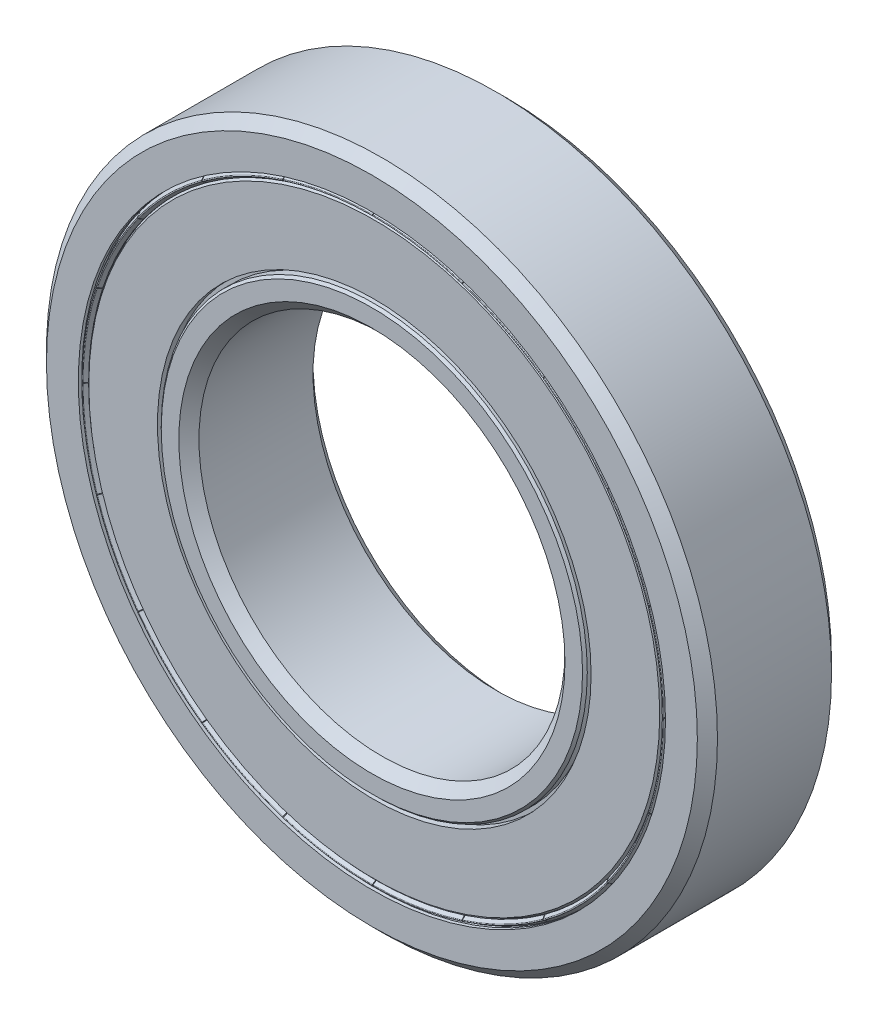
SolidWorks part; units mm, degrees
ref_plane "Front Plane" through (0, 0, 0) normal (0, 0, 1) x (1, 0, 0)
ref_plane "Top Plane" through (0, 0, 0) normal (0, 1, 0) x (1, 0, 0)
ref_plane "Right Plane" through (0, 0, 0) normal (1, 0, 0) x (0, 0, -1)
sketch "Sketch1" plane through (0, 0, 0) normal (0, 0, 1) x (1, 0, 0)
  circle A0 centre (0, 0) radius 30
  circle A1 centre (0, 0) radius 55
  dimension "OD" = 110
  dimension "ID" = 60
sketch "Sketch2" plane through (0, 0, 0) normal (1, 0, 0) x (0, 0, -1)
  line L0 (-11, 55) -> (11, 55)
  line L1 (-11, 30) -> (-11, -30) construction
  line L2 (11, 55) -> (11, -55) construction
  line L3 (-11, 0) -> (11, 0) construction
  line L6 (0, 55) -> (0, 30) construction
  circle A0 centre (0, 42.5) radius 8.75 construction
  point P8 (0, 55)
  dimension "Approx. Ball Dia." = 17.5
  dimension "Width" = 22
  dimension "For Shaft Diameter" = 60
  dimension "For Housing ID" = 110
sketch "Sketch3" plane through (0, 0, 0) normal (1, 0, 0) x (0, 0, -1)
  line L0 (0, 0) -> (0, 60) construction
  line L1 (-11, 30) -> (-11, -30) construction
  line L2 (9.35, 55) -> (-9.35, 55)
  line L3 (-9.35, 55) -> (-11, 53.35)
  line L4 (-11, 53.35) -> (-11, 48.1276)
  line L5 (-11, 48.1276) -> (-10.45, 48.1276)
  line L6 (-10.45, 48.1276) -> (-10.45, 49.6888)
  line L7 (-10.45, 49.6888) -> (-10.0611, 50.0777)
  line L8 (-10.0611, 50.0777) -> (-4.375, 50.0777)
  line L10 (-11, 55) -> (11, 55) construction
  line L12 (-10.45, 49.6888) -> (-10.45, 51.25) construction
  line L13 (10.0611, 50.0777) -> (4.375, 50.0777)
  line L14 (10.45, 49.6888) -> (10.0611, 50.0777)
  line L15 (10.45, 48.1276) -> (10.45, 49.6888)
  line L16 (11, 48.1276) -> (10.45, 48.1276)
  line L17 (11, 53.35) -> (11, 48.1276)
  line L18 (9.35, 55) -> (11, 53.35)
  line L19 (9.35, 30) -> (-9.35, 30)
  line L20 (-9.35, 30) -> (-11, 31.65)
  line L21 (-11, 31.65) -> (-11, 34.5334)
  line L22 (-11, 34.5334) -> (-10.6111, 34.9223)
  line L23 (-10.6111, 34.9223) -> (-4.375, 34.9223)
  line L25 (10.6111, 34.9223) -> (4.375, 34.9223)
  line L26 (11, 34.5334) -> (10.6111, 34.9223)
  line L27 (11, 31.65) -> (11, 34.5334)
  line L28 (9.35, 30) -> (11, 31.65)
  circle A2 centre (0, 42.5) radius 8.75 construction
  arc A3 (-4.375, 50.0777) -> (4.375, 50.0777) centre (0, 42.5) cw
  arc A4 (-4.375, 34.9223) -> (4.375, 34.9223) centre (0, 42.5) ccw
  point P5 (0, 51.25)
  point P31 (0, 55)
  point P37 (0, 30)
  dimension "D1" = 45
  dimension "D2" = 0.55
  dimension "D3" = 8.75
  dimension "D4" = 1.65
revolve "Revolve1" add sketch "Sketch3" angle 360 about L3
sketch "Sketch4" plane through (0, 0, 0) normal (1, 0, 0) x (0, 0, -1)
  line L0 (0, 51.25) -> (0, 33.75)
  line L1 (0, 55) -> (0, 30) construction
  circle A0 centre (0, 42.5) radius 8.75 construction
  arc A1 (0, 33.75) -> (0, 51.25) centre (0, 42.5) cw
revolve "Revolve2" add sketch "Sketch4" angle 360 about L6
pattern_circular "CirPattern1" count 10 over 360 about axis through (0, 0, 11) along (0, 0, -1) of bodies 106
sketch "Sketch5" plane through (0, 0, 0) normal (1, 0, 0) x (0, 0, -1)
  line L0 (-8.75, 42.5) -> (-8.75, 34.9223) construction
  line L1 (-10.6111, 34.9223) -> (-4.375, 34.9223) construction
  line L3 (-8.75, 34.9223) -> (-9.3704, 34.9223)
  line L4 (-9.3704, 34.9223) -> (-9.3704, 35.5426)
  line L5 (-9.3704, 35.5426) -> (-10.6111, 35.5426)
  line L6 (-10.6111, 35.5426) -> (-10.6111, 46.7909)
  line L7 (-10.6111, 46.7909) -> (-9.3704, 47.5073)
  line L8 (-9.3704, 47.5073) -> (-8.75, 47.5073)
  line L9 (-8.75, 47.5073) -> (-8.75, 34.9223)
  line L10 (0, 42.5) -> (0, 55) construction
  line L11 (9.3704, 47.5073) -> (8.75, 47.5073)
  line L12 (10.6111, 46.7909) -> (9.3704, 47.5073)
  line L13 (10.6111, 35.5426) -> (10.6111, 46.7909)
  line L14 (9.3704, 35.5426) -> (10.6111, 35.5426)
  line L15 (9.3704, 34.9223) -> (9.3704, 35.5426)
  line L16 (8.75, 34.9223) -> (9.3704, 34.9223)
  line L17 (8.75, 47.5073) -> (8.75, 34.9223)
  line L18 (-10.6111, 46.7909) -> (-9.9907, 46.7909) construction
  line L19 (-9.9907, 46.7909) -> (-9.3704, 46.7909) construction
  line L20 (-9.3704, 46.7909) -> (-8.75, 46.7909) construction
  line L21 (-9.3704, 47.5073) -> (-9.3704, 48.1276) construction
  circle A0 centre (0, 42.5) radius 8.75 construction
  dimension "D1" = 30
revolve "Revolve3" add sketch "Sketch5" angle 360 about L3
sketch "Sketch6" plane through (0, 0, 0) normal (1, 0, 0) x (0, 0, -1)
  line L0 (-10.0017, 48.1276) -> (-10.0375, 48.1276)
  line L1 (-10.0375, 48.1276) -> (-11, 47.5719)
  line L2 (-11, 47.5719) -> (-10.3317, 47.104)
  line L4 (-10.6111, 46.7909) -> (-9.3704, 47.5073) construction
  line L5 (-10.0017, 47.1428) -> (-10.0017, 48.1276)
  line L6 (-11, 48.1276) -> (-10.45, 48.1276) construction
  line L7 (-10.3317, 47.104) -> (-10.2217, 47.104)
  line L8 (-10.2217, 47.104) -> (-10.0017, 47.1428)
  line L9 (-11, 53.35) -> (-11, -53.35) construction
  line L11 (-10.2217, 47.104) -> (-10.1117, 47.104) construction
  line L12 (-10.1117, 47.104) -> (-10.0017, 47.104) construction
  point P27 (-10.0196, 48.1276)
  dimension "D1" = 30
  dimension "D3" = 10
  dimension "D2" = 35
  dimension "D4" = 0.11
  dimension "D5" = 0.9625
revolve "Revolve4" add sketch "Sketch6" angle 360 about L3
fillet "Fillet1" radius 0.11 1 edges at (47.5719, 0, 11)
sketch "Sketch7" plane through (0, 0, 0) normal (0, 0, 1) x (1, 0, 0)
  line L0 (-0.05, 48.1276) -> (-0.05, 48.2276)
  line L1 (-0.05, 48.1276) -> (0.05, 48.1276) construction
  line L2 (-0.05, 48.1276) -> (-0.05, 47.104)
  line L3 (-0.05, 47.104) -> (0.05, 47.104) construction
  line L4 (0.05, 48.1276) -> (0.05, 47.104)
  line L5 (-0.05, 48.2276) -> (0.05, 48.2276)
  line L6 (0.05, 48.2276) -> (0.05, 48.1276)
  line L7 (-0.05, 47.104) -> (-0.05, 47.004)
  line L8 (-0.05, 47.004) -> (0.05, 47.004)
  line L9 (0.05, 47.004) -> (0.05, 47.104)
  dimension "D1" = 0.1
extrude "Cut-Extrude1" cut sketch "Sketch7" along normal through all from vertex starting at point (0, 48.1276, 10.0196)
pattern_circular "CirPattern2" count 20 over 360 about axis through (0, 0, 11) along (0, 0, -1) of "Cut-Extrude1"
mirror "Mirror1" about plane through (0, 0, 0) normal (0, 0, 1) of bodies 120
equation "\"Approx. Ball Dia.@Sketch2\"=( \"OD@Sketch1\" - \"ID@Sketch1\" )  * .5 * .7"
equation "\"D2@Sketch3\"=\"Width@Sketch2\"*.025"
equation "\"D3@Sketch3\"=\"Approx. Ball Dia.@Sketch2\"*.5"
equation "\"D4@Sketch3\"=\"Width@Sketch2\"*.075"
equation "\"Approx No of Balls\"= ( pi * \"OD@Sketch1\" ) * .5 / \"Approx. Ball Dia.@Sketch2\""
equation "\"D1@CirPattern1\"=\"Approx No of Balls\""
equation "\"D4@Sketch6\"=\"D2@Sketch3\"*.2"
equation "\"D1@CirPattern2\"=\"Approx No of Balls\"*2"
equation "\"D5@Sketch6\"=\"D2@Sketch3\"*1.75"
equation "\"D1@Fillet1\"=\"d4@sketch6\""
